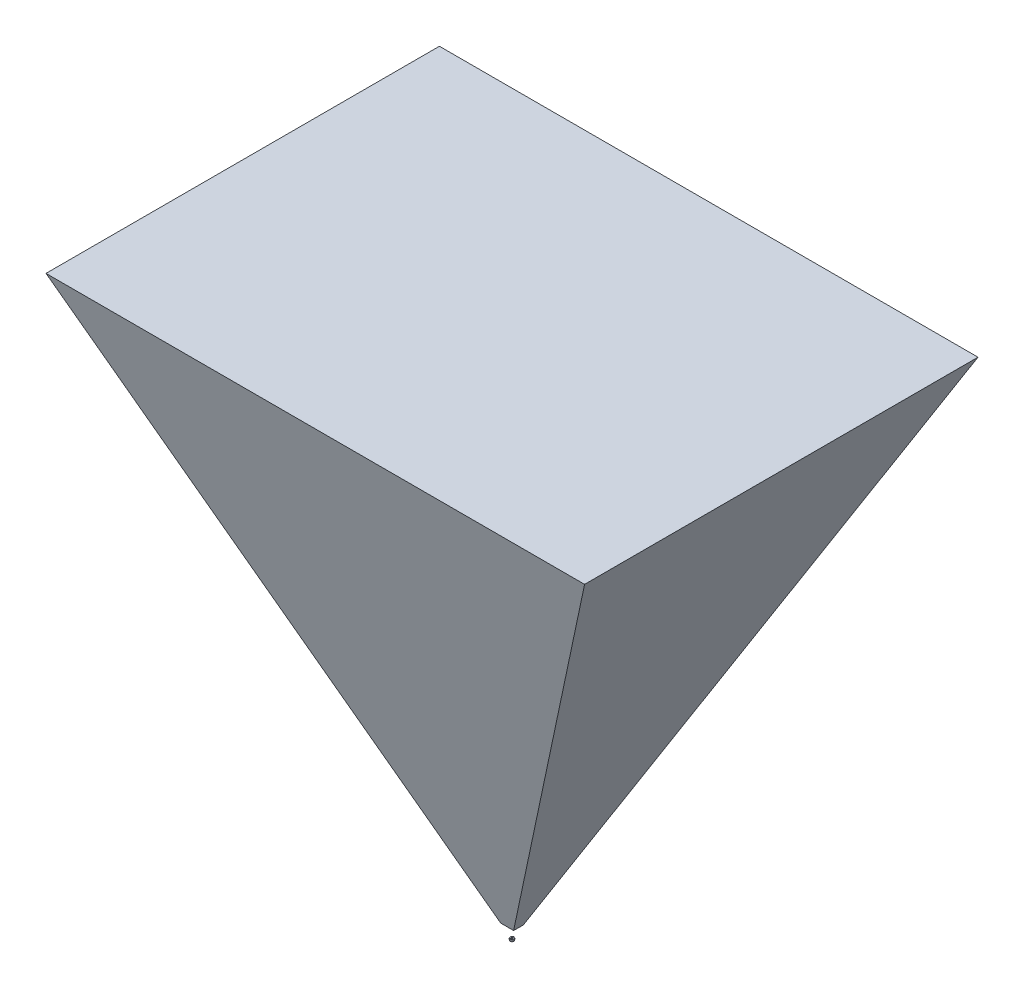
SolidWorks part; units mm, degrees
material "ABS PC"
ref_plane "Vorne" through (0, 0, 0) normal (0, 0, 1) x (1, 0, 0)
ref_plane "Oben" through (0, 0, 0) normal (0, 1, 0) x (1, 0, 0)
ref_plane "Rechts" through (0, 0, 0) normal (1, 0, 0) x (0, 0, -1)
sketch "Skizze3" plane through (0, 0, 0) normal (0, 0, 1) x (1, 0, 0)
  line L0 (0, 0) -> (0, -2.1568) construction
  line L1 (1, 0.8) -> (2.75, 0.8)
  line L2 (2.75, 0.8) -> (2.75, -2.55)
  line L3 (2.75, -2.55) -> (2.1, -2.55)
  line L4 (1, 0.8) -> (0.625, 0.425)
  line L5 (0.8125, 0.6125) -> (0.8125, 0.8) construction
  line L6 (0.8125, 0.8) -> (1, 0.8) construction
  line L7 (2.1, -2.55) -> (1.8, -2.25)
  line L8 (2.1, -2.55) -> (2.1, -2.4) construction
  line L9 (2.1, -2.4) -> (1.95, -2.4) construction
  line L10 (0, -2.55) -> (0, 0.525)
  arc A0 (1.8, -2.25) -> (0, -2.55) centre (0, 3) cw
  arc A1 (0, 0.525) -> (0.625, 0.425) centre (0, -1.4781) cw
  dimension "D6" = 0.1
  dimension "D1" = 3.35
  dimension "D2" = 5.5
  dimension "D3" = 2
  dimension "D4" = 1.25
  dimension "D5" = 3.6
  dimension "D7" = 0.8
  dimension "D8" = 0.3
revolve "Body" add sketch "Skizze3" angle 360 about L0
sketch "Skizze4" plane through (0, 0, 0) normal (0, 0, 1) x (1, 0, 0)
  line L0 (0, 0) -> (0, 1.3093) construction
  line L1 (2.75, -2.55) -> (2.75, 0.8) construction
  line L2 (2.75, -0.2) -> (3, -0.2)
  line L3 (2.75, -0.2) -> (2.75, -1.2)
  line L4 (2.75, -1.2) -> (3, -1.2)
  line L5 (3, -0.2) -> (3, -1.2)
  line L6 (2.75, 0.8) -> (-2.75, 0.8) construction
  dimension "D1" = 2
  dimension "D2" = 1
  dimension "D3" = 6
revolve "Thread" add sketch "Skizze4" angle 360 about L0
sketch "Skizze5" plane through (0, 0, 0) normal (1, 0, 0) x (0, 0, -1)
  line L0 (0, 0) -> (0, -3.7681) construction
  line L1 (2.75, 0.8) -> (2.75, 0.35)
  line L2 (2.75, -0.2) -> (2.75, 0.8) construction
  line L3 (2.75, 0.35) -> (2.3, 0.8)
  line L4 (2.75, 0.8) -> (-2.75, 0.8) construction
  line L5 (2.3, 0.8) -> (2.75, 0.8)
  dimension "D1" = 0.45
revolve "Toolface" cut sketch "Skizze5" angle 60 about L0
pattern_circular "Kreismuster1" count 3 over 360 of "Toolface"
sketch "Skizze6" plane through (0, 0, 0) normal (1, 0, 0) x (0, 0, -1)
  line L0 (0, 0) -> (0, 10.2784) construction
  line L1 (-7.2794, 18.7078) -> (-298.4556, 818.7078)
  line L2 (-298.4556, 818.7078) -> (298.4556, 818.7078)
  line L3 (-7.2794, 18.7078) -> (7.2794, 18.7078)
  line L4 (0, 818.7078) -> (0, 18.7078) construction
  line L5 (-7.2794, 18.7078) -> (0, -1.2922) construction
  line L8 (7.2794, 18.7078) -> (298.4556, 818.7078)
  point P3 (-0.625, 0.425)
  dimension "D1" = 800
  dimension "D2" = 20
  dimension "D3" = 40
extrude "FOV - 3,6mm f/2,9" add sketch "Skizze6" along normal mid plane 1000 separate body
sketch "Skizze8" plane through (0, 0, 0) normal (0, 0, 1) x (1, 0, 0)
  line L0 (0, 0) -> (0, 233.3089) construction
  line L1 (-9.7405, 18.7078) -> (-408.6058, 818.7078)
  line L2 (500, 18.7078) -> (-500, 18.7078) construction
  line L3 (500, 818.7078) -> (-500, 818.7078) construction
  line L4 (-408.6058, 818.7078) -> (408.6058, 818.7078)
  line L5 (-9.7405, 18.7078) -> (9.7405, 18.7078)
  line L8 (9.7405, 18.7078) -> (408.6058, 818.7078)
  circle A0 centre (0, 0) radius 5
  point P9 (-0.625, 0.425)
  point P16 (0, 18.7078)
  point P17 (0, 818.7078)
  dimension "D2" = 10
  dimension "D1" = 53
extrude "FOV2" cut sketch "Skizze8" against normal through all and the other way through all flip side to cut
